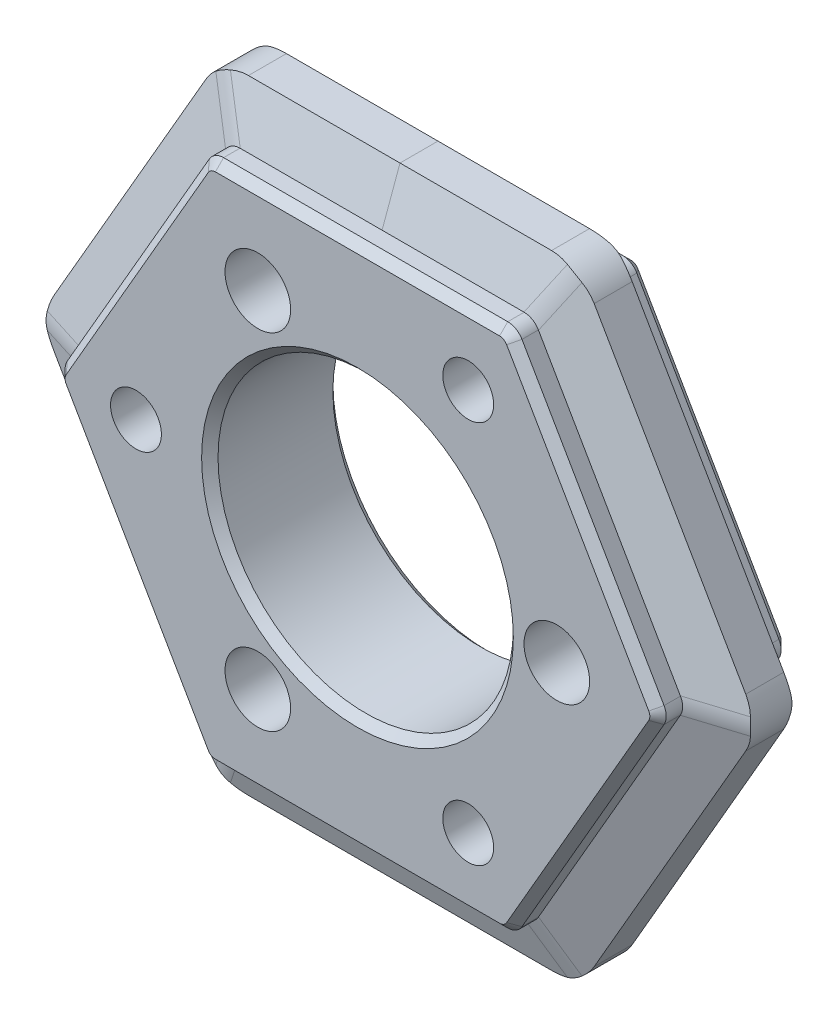
SolidWorks part; units mm, degrees
material "6061 合金"
ref_plane "前视基准面" through (0, 0, 0) normal (0, 0, 1) x (1, 0, 0)
ref_plane "上视基准面" through (0, 0, 0) normal (0, 1, 0) x (1, 0, 0)
ref_plane "右视基准面" through (0, 0, 0) normal (1, 0, 0) x (0, 0, -1)
other "Configuration Table"
sketch "草图2" plane through (0, 0, 0) normal (0, 0, 1) x (1, 0, 0)
  line L1 (9.2376, 16) -> (-9.2376, 16)
  line L2 (-9.2376, 16) -> (-18.4752, 0)
  line L3 (-18.4752, 0) -> (-9.2376, -16)
  line L4 (-9.2376, -16) -> (9.2376, -16)
  line L5 (9.2376, -16) -> (18.4752, 0)
  line L6 (18.4752, 0) -> (9.2376, 16)
  circle A0 centre (0, 0) radius 16 construction
  dimension "D1" = 32
extrude "凸台-拉伸1" add sketch "草图2" along normal blind 2.5 and the other way blind 5.5
hole_wizard "M3 六角圆柱头螺钉的柱形沉头孔1" positions "草图4" profile "草图5" counterbore size "M3" standard "GB" end condition through all
sketch "草图4" plane through (0, 0, -5.5) normal (0, 0, -1) x (-1, 0, 0)
  line L0 (-18.4752, 0) -> (0, 0) construction
  line L1 (0, 0) -> (-6.75, 11.6913) construction
  circle A0 centre (0, 0) radius 13.5
  point P0 (-6.75, 11.6913)
  point P24 (13.5, 0)
  point P25 (-6.75, -11.6913)
  dimension "D1" = 27
  dimension "D2" = 60
  dimension "D3" = 3
sketch "草图5" plane through (6.75, 11.6913, -5.5) normal (1, 0, 0) x (0, 1, 0)
  line L0 (0, 0) -> (0, 8)
  line L1 (0, 8) -> (1.55, 8)
  line L3 (1.55, 8) -> (1.55, 3.1)
  line L4 (1.55, 3.1) -> (3, 3.1)
  line L5 (3, 3.1) -> (3, 0)
  line L7 (3, 0) -> (0, 0)
  line L11 (0, -6.35) -> (0, 107.95) construction
  dimension "通孔孔直径" = 3.1
  dimension "通孔孔深度" = 8
  dimension "柱形沉头孔直径" = 6
  dimension "柱形沉头孔深度" = 3.1
hole_wizard "Ø4.0mm 暗销孔1" positions "草图6" profile "草图7" hole size "Ø4.0" standard "GB"
sketch "草图6" plane through (0, 0, 2.5) normal (0, 0, 1) x (1, 0, 0)
  line L0 (-23.5778, 0) -> (0, 0) construction
  line L1 (0, 0) -> (-6.075, 10.5222) construction
  circle A0 centre (0, 0) radius 12.15
  point P0 (-6.075, 10.5222)
  point P19 (12.15, 0)
  point P20 (-6.075, -10.5222)
  dimension "D1" = 24.3
  dimension "D2" = 60
  dimension "D3" = 3
sketch "草图7" plane through (-6.075, 10.5222, 2.5) normal (1, 0, 0) x (0, -1, 0)
  line L0 (0, 0) -> (0, 4.2017)
  line L1 (0, 4.2017) -> (2, 3)
  line L2 (2, 3) -> (2, 0)
  line L5 (2, 0) -> (0, 0)
  line L10 (0, 4.2017) -> (-2, 3) construction
  line L11 (0, -6.35) -> (0, 107.95) construction
  dimension "孔直径" = 4
  dimension "孔深度" = 3
  dimension "导头角度" = 118
sketch "草图8" plane through (0, 0, 2.5) normal (0, 0, 1) x (1, 0, 0)
  circle A0 centre (0, 0) radius 9
  dimension "D1" = 18
extrude "切除-拉伸1" cut sketch "草图8" against normal through all
ref_plane "基准面1" through (0, 0, -2.5) normal (0, 0, -1) x (-1, 0, 0)
sketch "草图10" plane through (0, 0, -2.5) normal (0, 0, -1) x (-1, 0, 0)
  line L6 (-9.2376, 16) -> (-18.4752, 0)
  line L7 (-18.4752, 0) -> (-9.2376, -16)
  line L8 (-9.2376, -16) -> (9.2376, -16)
  line L9 (9.2376, -16) -> (18.4752, 0)
  line L10 (18.4752, 0) -> (9.2376, 16)
  line L11 (9.2376, 16) -> (-9.2376, 16)
  line L12 (-9.2376, 16) -> (-18.4752, 0)
  line L13 (-18.4752, 0) -> (-9.2376, -16)
  line L14 (-9.2376, -16) -> (9.2376, -16)
  line L15 (9.2376, -16) -> (18.4752, 0)
  line L16 (18.4752, 0) -> (9.2376, 16)
  line L17 (9.2376, 16) -> (-9.2376, 16)
  dimension "D1" = 0
sketch "草图11" plane through (0, 0, 0) normal (1, 0, 0) x (0, 0, -1)
  line L0 (5.5, 0) -> (5.5, 16) construction
  line L1 (1.25, 16) -> (1.25, -0.3955) construction
  line L2 (-1, 16) -> (0.0919, 19)
  line L3 (-2.5, 16) -> (5.5, 16) construction
  line L4 (0.0919, 19) -> (2.4081, 19)
  line L5 (2.4081, 19) -> (3.5, 16)
  line L6 (3.5, 16) -> (-1, 16)
  dimension "D1" = 3
  dimension "D2" = 40
  dimension "D3" = 4.5
  dimension "D4" = 4.25
sweep "扫描1" add profiles "草图11" path "草图10"
fillet "圆角1" radius 3 18 edges at (10.9697, 19, -1.25) (21.9393, 0, -1.25) (10.9697, -19, -1.25) (-10.9697, -19, -1.25) (-21.9393, 0, -1.25) (-10.9697, 19, -1.25) (-10.1036, -17.5, -2.954) (10.1036, -17.5, -2.954) (20.2073, 0, -2.954) (10.1036, 17.5, -2.954) (-10.1036, 17.5, -2.954) (-20.2073, 0, -2.954) (10.1036, 17.5, 0.454) (-10.1036, 17.5, 0.454) (-20.2073, 0, 0.454) (-10.1036, -17.5, 0.454) (10.1036, -17.5, 0.454) (20.2073, 0, 0.454)
fillet "圆角2" radius 1 12 edges at (-9.2376, -16, 1.7265) (9.2376, -16, 1.7265) (18.4752, 0, 1.7265) (9.2376, 16, 1.7265) (-9.2376, 16, 1.7265) (-18.4752, 0, 1.7265) (-18.4752, 0, -4.4765) (-9.2376, -16, -4.4765) (9.2376, -16, -4.4765) (18.4752, 0, -4.4765) (9.2376, 16, -4.4765) (-9.2376, 16, -4.4765)
chamfer "倒角1" distance 0.5 angle 45 26 edges at (9, 0, 2.5) (9, 0, -5.5) (-13.8564, 8, 2.5) (-18.3205, 0, 2.5) (-9.1603, 15.866, 2.5) (-13.8564, -8, 2.5) (0, 16, 2.5) (-9.1603, -15.866, 2.5) (9.1603, 15.866, 2.5) (0, -16, 2.5) (13.8564, 8, 2.5) (9.1603, -15.866, 2.5) (18.3205, 0, 2.5) (13.8564, -8, 2.5) (0, 16, -5.5) (-9.1603, 15.866, -5.5) (9.1603, 15.866, -5.5) (-13.8564, 8, -5.5) (13.8564, 8, -5.5) (-18.3205, 0, -5.5) (18.3205, 0, -5.5) (-13.8564, -8, -5.5) (13.8564, -8, -5.5) (-9.1603, -15.866, -5.5) (9.1603, -15.866, -5.5) (0, -16, -5.5)
